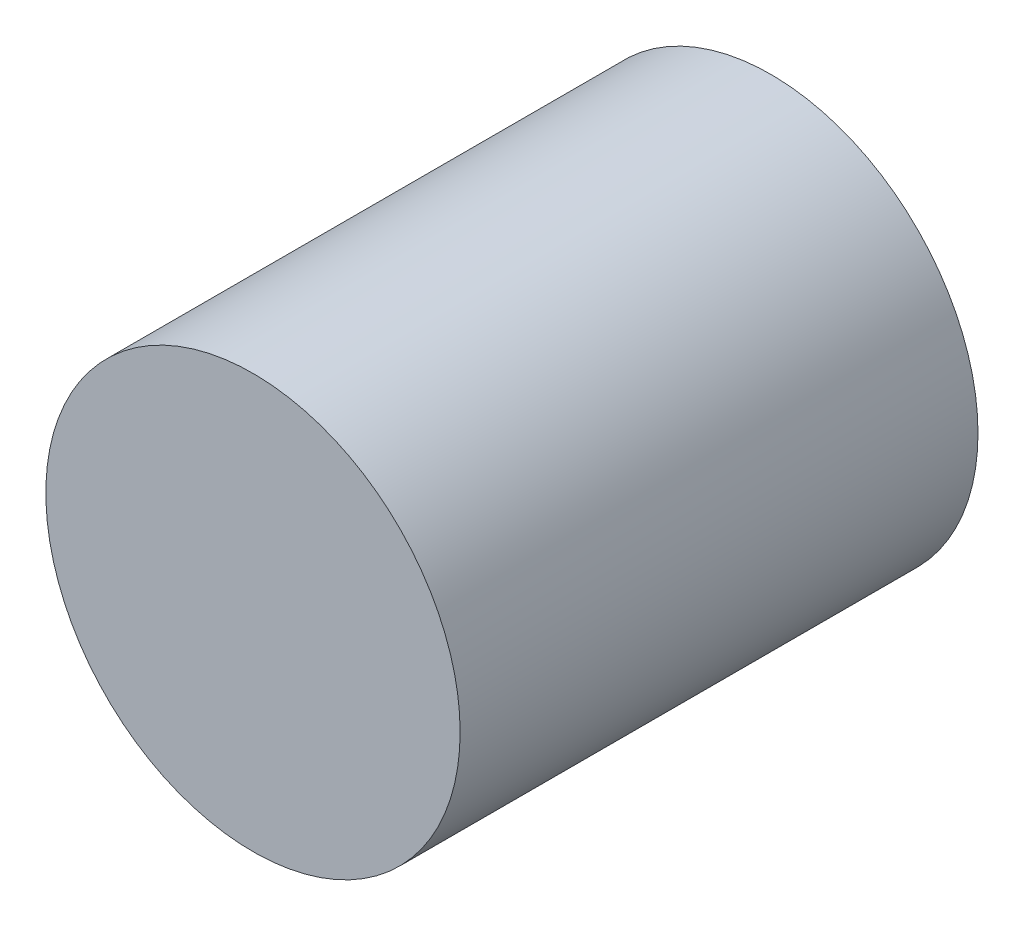
SolidWorks part; units mm, degrees
ref_plane "Front Plane" through (0, 0, 0) normal (0, 0, 1) x (1, 0, 0)
ref_plane "Top Plane" through (0, 0, 0) normal (0, 1, 0) x (1, 0, 0)
ref_plane "Right Plane" through (0, 0, 0) normal (1, 0, 0) x (0, 0, -1)
sketch "Sketch1" plane through (0, 0, 0) normal (0, 0, 1) x (1, 0, 0)
  circle A0 centre (0, 0) radius 6
  dimension "D1" = 12
extrude "Boss-Extrude1" add sketch "Sketch1" along normal blind 15
